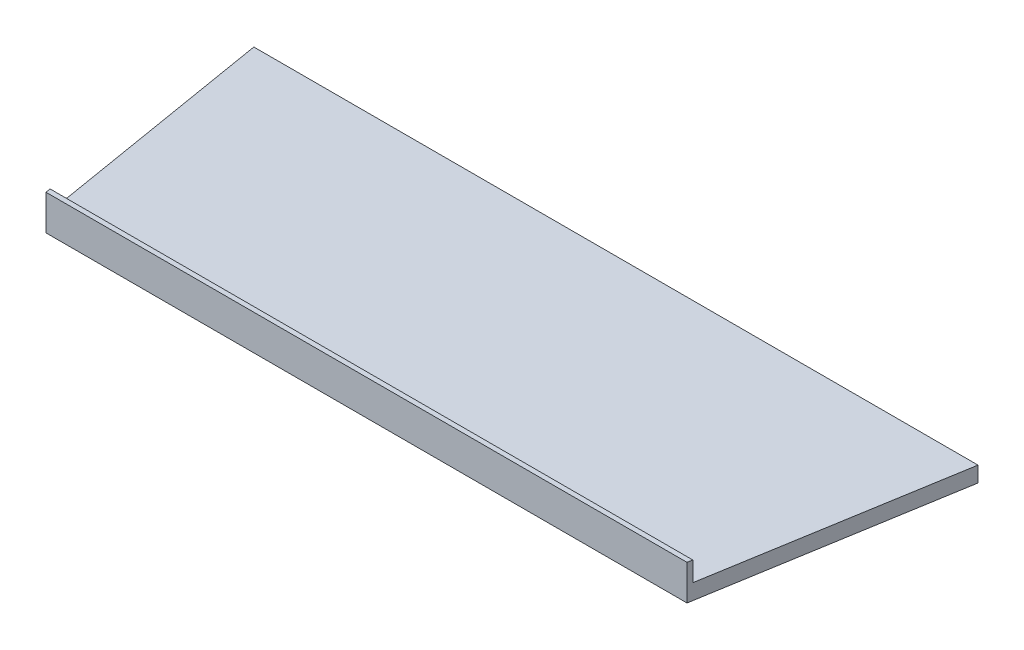
SolidWorks part; units mm, degrees
ref_plane "Front" through (0, 0, 0) normal (0, 0, 1) x (1, 0, 0)
ref_plane "Top" through (0, 0, 0) normal (0, 1, 0) x (1, 0, 0)
ref_plane "Right" through (0, 0, 0) normal (1, 0, 0) x (0, 0, -1)
sketch "Sketch1" plane through (0, 0, 0) normal (0, 1, 0) x (1, 0, 0)
  line L0 (-223.1356, -77.6924) -> (-248.5356, 74.7076)
  line L1 (-248.5356, 74.7076) -> (218.1894, 74.7076)
  line L2 (218.1894, 74.7076) -> (192.7894, -77.6924)
  line L3 (192.7894, -77.6924) -> (-223.1356, -77.6924)
  line L4 (-230.2091, -86.0424) -> (-258.3924, 83.0576)
  line L5 (-258.3924, 83.0576) -> (228.0462, 83.0576)
  line L6 (228.0462, 83.0576) -> (199.8629, -86.0424)
  line L7 (199.8629, -86.0424) -> (-230.2091, -86.0424)
  line L8 (-223.1356, -77.6924) -> (-221.7439, -86.0424)
  line L9 (192.7894, -77.6924) -> (191.3977, -86.0424)
  dimension "D1" = 466.725
  dimension "D2" = 415.925
  dimension "D3" = 152.4
  dimension "D4" = 8.35
extrude "Boss-Extrude1" add sketch "Sketch1" along normal blind 10 contours L9 L3 L8 L7 | L3 L0 L1 L2 region at (-15.1731, 0, 81.8628)
sketch "Sketch2" plane through (0, 10, 0) normal (0, 1, 0) x (1, 0, 0)
  line L0 (-221.7439, -86.0424) -> (191.3977, -86.0424)
  line L1 (191.3977, -86.0424) -> (191.9269, -82.8674)
  line L2 (218.1894, 74.7076) -> (191.3977, -86.0424) construction
  line L3 (191.9269, -82.8674) -> (-222.2731, -82.8674)
  line L4 (-248.5356, 74.7076) -> (-221.7439, -86.0424) construction
  line L5 (-222.2731, -82.8674) -> (-221.7439, -86.0424)
  dimension "D1" = 3.175
extrude "Boss-Extrude2" add sketch "Sketch2" along normal blind 12.7
